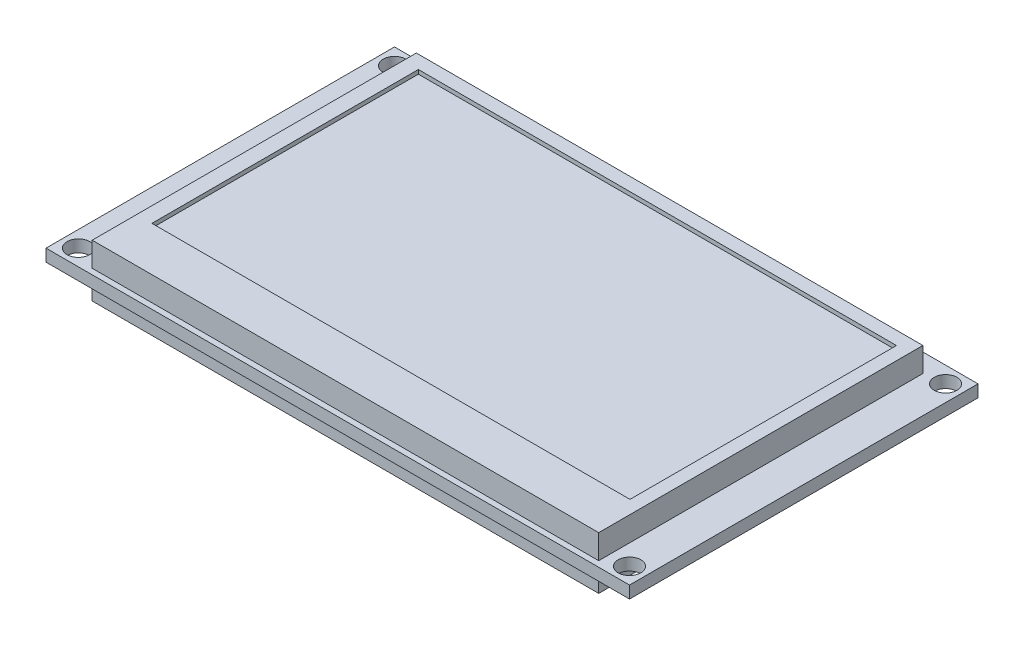
SolidWorks part; units mm, degrees
ref_plane "Front Plane" through (0, 0, 0) normal (0, 0, 1) x (1, 0, 0)
ref_plane "Top Plane" through (0, 0, 0) normal (0, 1, 0) x (1, 0, 0)
ref_plane "Right Plane" through (0, 0, 0) normal (1, 0, 0) x (0, 0, -1)
sketch "Sketch2" plane through (0, 0, 0) normal (0, 1, 0) x (1, 0, 0)
  line L1 (0, 0) -> (72, 0)
  line L2 (0, 0) -> (0, 43)
  line L3 (0, 43) -> (72, 43)
  line L4 (72, 0) -> (72, 43)
  dimension "D1" = 72
  dimension "D2" = 43
extrude "Boss-Extrude1" add sketch "Sketch2" along normal blind 1.5
sketch "Sketch3" plane through (0, 1.5, 0) normal (0, 1, 0) x (1, 0, 0)
  line L0 (0, 43) -> (0, 0) construction
  line L1 (72, 43) -> (0, 43) construction
  line L2 (72, 0) -> (72, 43) construction
  line L3 (0, 0) -> (72, 0) construction
  circle A0 centre (2, 41) radius 1.4
  circle A1 centre (70, 41) radius 1.4
  circle A2 centre (2, 2) radius 1.4
  circle A3 centre (70, 2) radius 1.4
  dimension "D3" = 2.8
  dimension "D5" = 2.8
  dimension "D7" = 2.8
  dimension "D8" = 2.8
  dimension "D1" = 2
  dimension "D2" = 2
  dimension "D4" = 2
  dimension "D6" = 2
extrude "Cut-Extrude1" cut sketch "Sketch3" against normal through all
sketch "Sketch4" plane through (0, 1.5, 0) normal (0, 1, 0) x (1, 0, 0)
  line L0 (0, 43) -> (0, 0) construction
  line L1 (5, 40.7) -> (67.5, 40.7)
  line L2 (5, 40.7) -> (5, 0.7)
  line L3 (5, 0.7) -> (67.5, 0.7)
  line L4 (67.5, 40.7) -> (67.5, 0.7)
  line L5 (72, 43) -> (0, 43) construction
  dimension "D1" = 62.5
  dimension "D2" = 5
  dimension "D3" = 40
  dimension "D4" = 2.3
extrude "Boss-Extrude2" add sketch "Sketch4" along normal blind 3
extrude "Boss-Extrude3" add sketch "Sketch4<2>" against normal blind 3.5
sketch "Sketch4<2>" plane through (0, 1.5, 0) normal (0, 1, 0) x (1, 0, 0) same geometry as "Sketch4"
sketch "Sketch8" plane through (0, 4.5, 0) normal (0, 1, 0) x (1, 0, 0)
  line L1 (6.885, 39.0622) -> (65.8748, 39.0622)
  line L2 (6.885, 39.0622) -> (6.885, 6.1827)
  line L3 (6.885, 6.1827) -> (65.8748, 6.1827)
  line L4 (65.8748, 39.0622) -> (65.8748, 6.1827)
extrude "Cut-Extrude2" cut sketch "Sketch8" against normal blind 0.5
